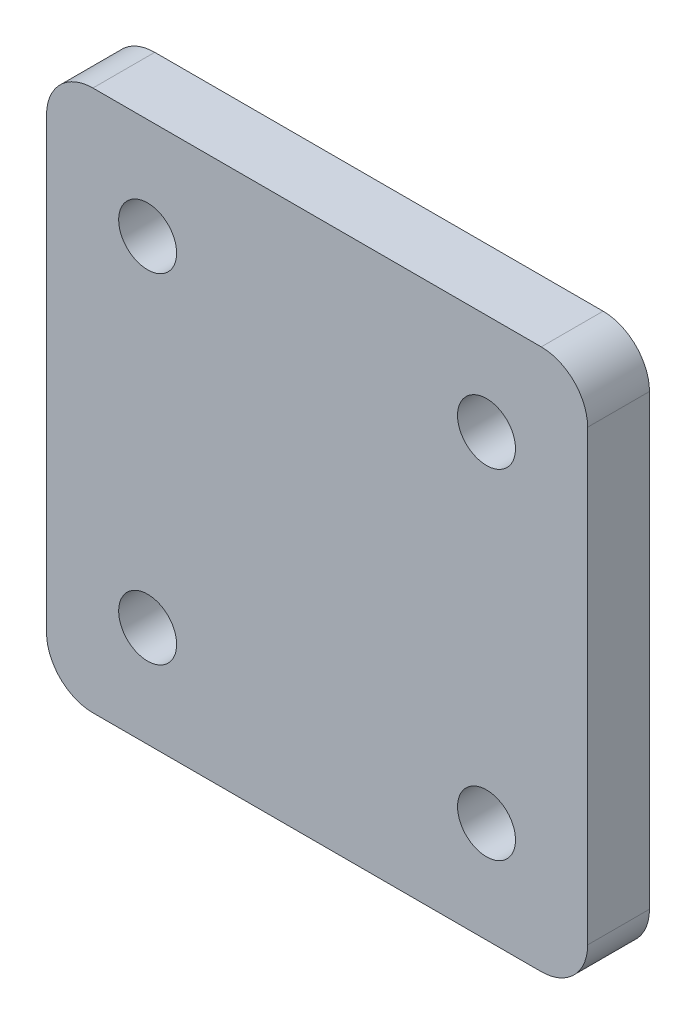
SolidWorks part; units mm, degrees
material "AISI 1020"
ref_plane "Спереди" through (0, 0, 0) normal (0, 0, 1) x (1, 0, 0)
ref_plane "Сверху" through (0, 0, 0) normal (0, 1, 0) x (1, 0, 0)
ref_plane "Справа" through (0, 0, 0) normal (1, 0, 0) x (0, 0, -1)
sketch "Эскиз1" plane through (0, 0, 0) normal (0, 0, 1) x (1, 0, 0)
  line L0 (-14.5, -17.5) -> (14.5, -17.5) construction
  line L1 (17.5, -14.5) -> (17.5, 14.5) construction
  line L2 (14.5, 17.5) -> (-14.5, 17.5) construction
  line L3 (-17.5, 14.5) -> (-17.5, -14.5) construction
  line L4 (-14.5, -17.5) -> (14.5, -17.5)
  line L5 (17.5, -14.5) -> (17.5, 14.5)
  line L6 (14.5, 17.5) -> (-14.5, 17.5)
  line L7 (-17.5, 14.5) -> (-17.5, -14.5)
  arc A0 (-17.5, -14.5) -> (-14.5, -17.5) centre (-14.5, -14.5) ccw construction
  arc A1 (14.5, -17.5) -> (17.5, -14.5) centre (14.5, -14.5) ccw construction
  arc A2 (17.5, 14.5) -> (14.5, 17.5) centre (14.5, 14.5) ccw construction
  arc A3 (-14.5, 17.5) -> (-17.5, 14.5) centre (-14.5, 14.5) ccw construction
  arc A4 (-17.5, -14.5) -> (-14.5, -17.5) centre (-14.5, -14.5) ccw
  arc A5 (14.5, -17.5) -> (17.5, -14.5) centre (14.5, -14.5) ccw
  arc A6 (17.5, 14.5) -> (14.5, 17.5) centre (14.5, 14.5) ccw
  arc A7 (-14.5, 17.5) -> (-17.5, 14.5) centre (-14.5, 14.5) ccw
base flange "Базовая кромка1" sketch "Эскиз1" thickness 4 reverse thickness direction yes parameters "D1"=0.74
hole_wizard "Отверстие обработанное метчиком M4x0.251" positions "Эскиз6" profile "Эскиз7" tap size "M4x0.25" standard "DIN"
sketch "Эскиз6" plane through (0, 0, 0) normal (0, 0, -1) x (-1, 0, 0)
  point P0 (-10.9602, 10.9602)
  point P3 (10.9602, 10.9602)
  point P6 (10.9602, -10.9602)
  point P9 (-10.9602, -10.9602)
sketch "Эскиз7" plane through (10.9602, 10.9602, 0) normal (1, 0, 0) x (0, 1, 0)
  line L0 (0, 0) -> (0, 10.3766)
  line L1 (0, 10.3766) -> (1.875, 9.25)
  line L2 (1.875, 9.25) -> (1.875, 0)
  line L5 (1.875, 0) -> (0, 0)
  line L10 (0, 10.3766) -> (-1.875, 9.25) construction
  line L11 (0, -6.35) -> (0, 107.95) construction
  dimension "Диаметр сверла" = 3.75
  dimension "Глубина сверла" = 9.25
  dimension "Угол заточки сверла" = 118
cosmetic thread "Отверстие резьбы1"
cosmetic thread "Отверстие резьбы2"
cosmetic thread "Отверстие резьбы3"
cosmetic thread "Отверстие резьбы4"
sketch "Сгиб-Линии1" plane through (0, 0, 0) normal (0, 1, 0) x (1, 0, 0)
sketch "Граничная рамка1" plane through (0, 0, 0) normal (0, 1, 0) x (1, 0, 0)
sheet metal parameters "Листовой металл3" thickness 4 parameters "D1"=0.74
flat pattern "Развертка3" [suppressed]
sketch "Сгиб-Линии2" plane through (0, 0, 0) normal (0, 1, 0) x (1, 0, 0)
sketch "Граничная рамка2" [suppressed] plane through (0, 0, 0) normal (0, 1, 0) x (1, 0, 0)
sheet metal parameters "Листовой металл4" thickness 4 parameters "D1"=0.74
flat pattern "Развертка3"
sketch "Сгиб-Линии2" plane through (0, 0, 0) normal (0, 1, 0) x (1, 0, 0)
sketch "Граничная рамка2" [suppressed] plane through (0, 0, 0) normal (0, 1, 0) x (1, 0, 0)
